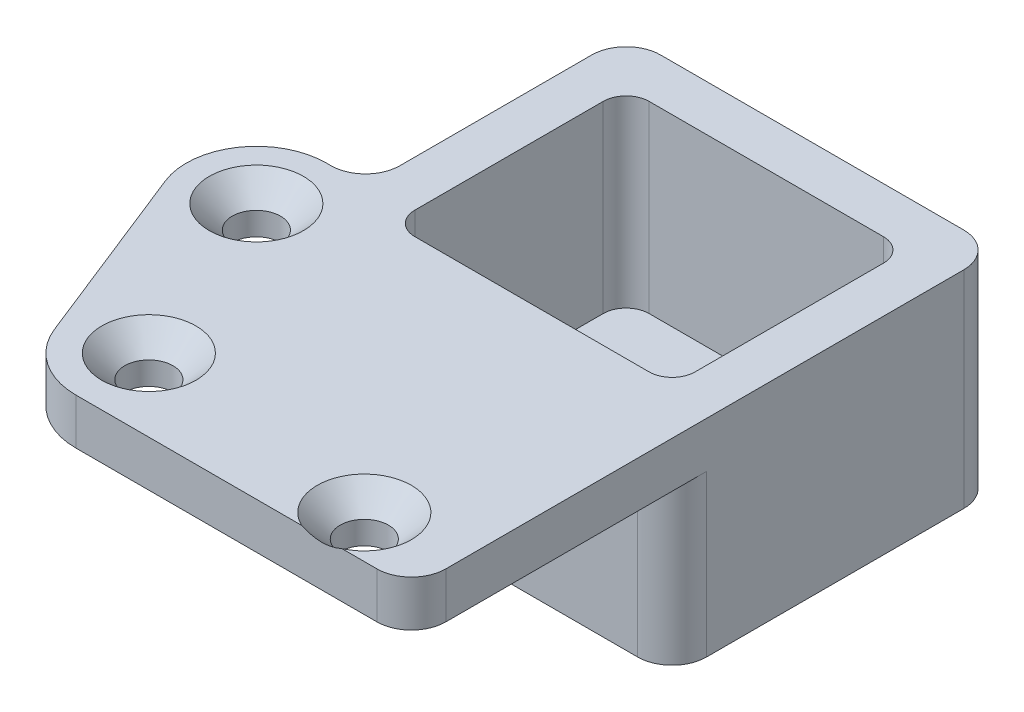
SolidWorks part; units mm, degrees
ref_plane "Front Plane" through (0, 0, 0) normal (0, 0, 1) x (1, 0, 0)
ref_plane "Top Plane" through (0, 0, 0) normal (0, 1, 0) x (1, 0, 0)
ref_plane "Right Plane" through (0, 0, 0) normal (1, 0, 0) x (0, 0, -1)
ref_axis "X-Axis" through (-88.4377, 0, 0) along (1, 0, 0)
ref_axis "Y-Axis" through (0, 0, -69.2525) along (0, 0, 1)
ref_axis "Z-Axis" through (0, -52.5493, 0) along (0, 1, 0)
sketch "Sketch1" plane through (0, 0, 0) normal (0, 1, 0) x (1, 0, 0)
  line L5 (-16.8344, -1.1263) -> (-13.646, -9.1506)
  line L6 (-12.3, 14.4) -> (3.9, 14.4)
  line L7 (-12.3, 14.4) -> (-12.3, 3.05)
  line L9 (3.9, 14.4) -> (3.9, 0.2)
  line L11 (-14, 3.05) -> (-12.3, 3.05)
  line L12 (3.9, -11.15) -> (3.9, 0.2)
  line L14 (-12.3, 14.4) -> (3.9, 0.2) construction
  line L15 (-10.7, -11.15) -> (3.9, -11.15)
  line L16 (-10.3, 12.4) -> (-12.3, 12.4) construction
  line L17 (-10.3, 2.2) -> (1.9, 2.2)
  line L18 (-10.3, 2.2) -> (-10.3, 12.4)
  line L19 (-10.3, 12.4) -> (1.9, 12.4)
  line L20 (1.9, 2.2) -> (1.9, 12.4)
  line L21 (-10.3, 2.2) -> (1.9, 12.4) construction
  line L22 (-10.3, 12.4) -> (1.9, 2.2) construction
  line L23 (-10.3, 12.4) -> (-10.3, 14.4) construction
  line L24 (-14, 0) -> (0, 0) construction
  line L25 (0, 0) -> (0, -9.3) construction
  circle A0 centre (-14, 0) radius 1.05
  circle A2 centre (0, -9.3) radius 1.05
  circle A3 centre (-10.7, -7.98) radius 1.05
  arc A4 (-14, 3.05) -> (-16.8344, -1.1263) centre (-14, 0) ccw
  circle A7 centre (-14, 0) radius 3.05 construction
  arc A8 (-13.646, -9.1506) -> (-10.7, -11.15) centre (-10.7, -7.98) ccw
  point P10 (-4.2, 7.3)
  point P14 (-4.2, 7.3)
  dimension "D5" = 2.1
  dimension "D9" = 9.8
  dimension "D1" = 14
  dimension "D2" = 9.3
  dimension "D3" = 10.7
  dimension "D4" = 1.32
  dimension "D6" = 2
  dimension "D7" = 16.6
  dimension "D11" = 1.85
  dimension "D13" = 12.2
  dimension "D14" = 10.2
  dimension "D8" = 2
extrude "Boss-Extrude1" add sketch "Sketch1" along normal blind 2
sketch "Sketch2" plane through (0, 0, 0) normal (0, -1, 0) x (1, 0, 0)
  line L10 (-10.3, -12.4) -> (-10.3, -14.4) construction
  line L11 (-10.3, -2.2) -> (-10.3, -0.2) construction
  line L12 (3.9, 11.15) -> (3.9, -14.4) construction
  line L13 (-12.3, -14.4) -> (3.9, -14.4)
  line L14 (-12.3, -14.4) -> (-12.3, -0.2)
  line L15 (-12.3, -0.2) -> (3.9, -0.2)
  line L16 (3.9, -14.4) -> (3.9, -0.2)
  line L17 (-12.3, -14.4) -> (3.9, -0.2) construction
  line L18 (-12.3, -0.2) -> (3.9, -14.4) construction
  line L19 (3.9, -14.4) -> (-12.3, -14.4) construction
  line L21 (-12.3, -14.4) -> (-12.3, -3.05) construction
  line L25 (-10.3, -12.4) -> (1.9, -12.4)
  line L26 (1.9, -12.4) -> (1.9, -2.2)
  line L27 (1.9, -2.2) -> (-10.3, -2.2)
  line L28 (-10.3, -2.2) -> (-10.3, -12.4)
  line L29 (-10.3, -12.4) -> (1.9, -12.4)
  line L30 (1.9, -12.4) -> (1.9, -2.2)
  line L31 (1.9, -2.2) -> (-10.3, -2.2)
  line L32 (-10.3, -2.2) -> (-10.3, -12.4)
  point P0 (-3.6903, -5.5)
  point P6 (-4.2, -7.3)
  dimension "D1" = 0
extrude "Boss-Extrude2" add sketch "Sketch2" along normal blind 7
sketch "Sketch4" plane through (0, -7, 0) normal (0, -1, 0) x (1, 0, 0)
  line L0 (-12.3, -14.4) -> (3.9, -0.2) construction
  line L1 (-12.3, -0.2) -> (3.9, -0.2)
  line L2 (-12.3, -0.2) -> (-12.3, -14.4)
  line L3 (-12.3, -14.4) -> (3.9, -14.4)
  line L4 (3.9, -0.2) -> (3.9, -14.4)
  circle A0 centre (-4.2, -7.3) radius 2
  dimension "D1" = 4
extrude "Boss-Extrude3" add sketch "Sketch4" against normal blind 1
fillet "Fillet1" radius 1.5 6 edges at (-12.3, -2.5, -14.4) (3.9, -2.5, -14.4) (3.9, 1, 11.15) (-12.3, 1, -3.05) (-12.3, -3.5, -0.2) (3.9, -3.5, -0.2)
sketch "Sketch5" plane through (0, -7, 0) normal (0, -1, 0) x (1, 0, 0)
  line L0 (-12.3, -1.7) -> (-12.3, -4.55) construction
  line L1 (-12.3, -2.3758) -> (-12.3, -0.2)
  line L2 (-12.3, -0.2) -> (-9.8404, -0.2)
  line L3 (2.4, -0.2) -> (-10.8, -0.2) construction
  line L4 (-12.3, -1.7) -> (-12.3, -12.9) construction
  line L5 (2.4, -0.2) -> (-10.8, -0.2) construction
  line L6 (-12.3, -2.3758) -> (-9.8404, -0.2)
  line L7 (-12.3, -1.7) -> (-12.3, -4.55) construction
  line L14 (2.4, -0.2) -> (-10.8, -0.2)
  line L15 (-12.3, -1.7) -> (-12.3, -12.9)
  line L16 (-10.8, -14.4) -> (2.4, -14.4)
  line L17 (3.9, -12.9) -> (3.9, -1.7)
  line L18 (2.4, -0.2) -> (-10.8, -0.2) construction
  line L19 (-12.3, -1.7) -> (-12.3, -12.9) construction
  line L20 (-10.8, -14.4) -> (2.4, -14.4) construction
  line L21 (3.9, -12.9) -> (3.9, -1.7) construction
  arc A8 (-10.8, -0.2) -> (-12.3, -1.7) centre (-10.8, -1.7) ccw
  arc A9 (-12.3, -12.9) -> (-10.8, -14.4) centre (-10.8, -12.9) ccw
  arc A10 (2.4, -14.4) -> (3.9, -12.9) centre (2.4, -12.9) ccw
  arc A11 (3.9, -1.7) -> (2.4, -0.2) centre (2.4, -1.7) ccw
  arc A12 (-10.8, -0.2) -> (-12.3, -1.7) centre (-10.8, -1.7) ccw construction
  arc A13 (-12.3, -12.9) -> (-10.8, -14.4) centre (-10.8, -12.9) ccw construction
  arc A14 (2.4, -14.4) -> (3.9, -12.9) centre (2.4, -12.9) ccw construction
  arc A15 (3.9, -1.7) -> (2.4, -0.2) centre (2.4, -1.7) ccw construction
  dimension "D1" = 0
extrude "Cut-Extrude1" cut sketch "Sketch5" against normal up to surface (7 mm away) up to face at (-14, 0, 1.05)
fillet "Fillet2" radius 2 2 edges at (-9.8404, -3.5, -0.2) (-12.3, -3.5, -2.3758)
fillet "Fillet3" radius 1 4 edges at (-10.3, -2, -2.2) (1.9, -2, -2.2) (1.9, -2, -12.4) (-10.3, -2, -12.4)
chamfer "Chamfer2" distance 1 angle 45 3 edges at (0, 2, 10.35) (-10.7, 2, 9.03) (-14, 2, 1.05)
sketch "Sketch6" plane through (0, -7, 0) normal (0, -1, 0) x (1, 0, 0)
  line L1 (-9.2, -11.3) -> (0.8, -11.3) construction
  line L2 (-9.2, -11.3) -> (-9.2, -3.3) construction
  line L3 (-9.2, -3.3) -> (0.8, -3.3) construction
  line L4 (0.8, -11.3) -> (0.8, -3.3) construction
  line L5 (-9.2, -11.3) -> (0.8, -3.3) construction
  line L6 (-9.2, -3.3) -> (0.8, -11.3) construction
  circle A0 centre (-9.2, -7.3) radius 0.8
  circle A1 centre (0.8, -7.3) radius 0.8
  point P0 (-4.2, -7.3)
  dimension "D1" = 1.6
  dimension "D2" = 8
  dimension "D3" = 10
extrude "Cut-Extrude2" cut sketch "Sketch6" against normal up to surface (1 mm away) up to face at (-4.2, -6, -7.3)
chamfer "Chamfer3" distance 0.8 angle 45 2 edges at (-9.2, -7, -8.1) (0.8, -7, -8.1)
